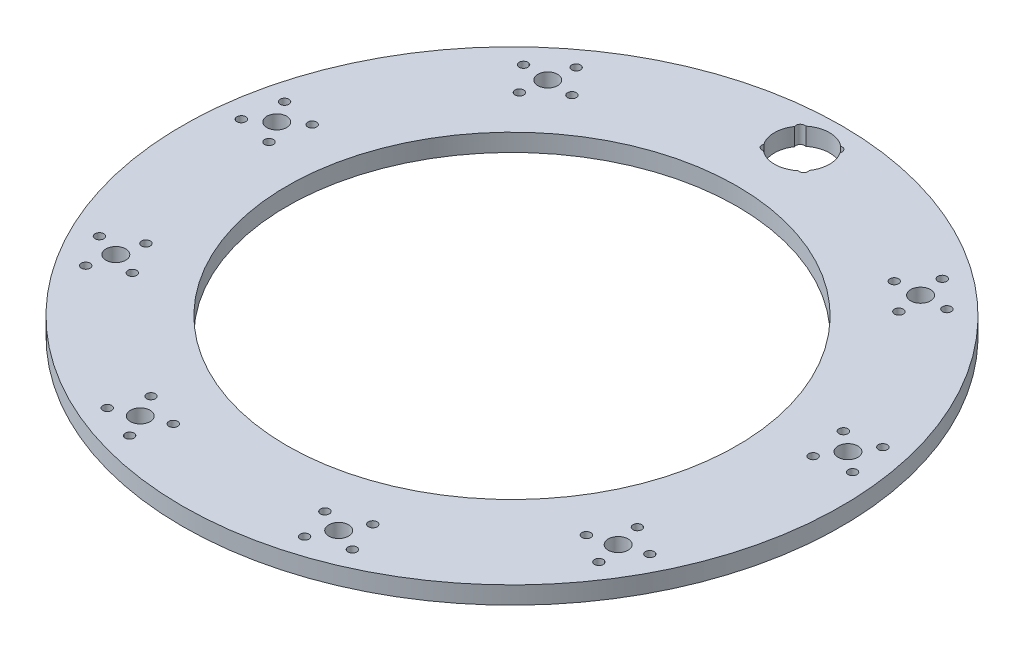
SolidWorks part; units mm, degrees
material "Balsa"
ref_plane "Ebene vorne" through (0, 0, 0) normal (0, 0, 1) x (1, 0, 0)
ref_plane "Ebene oben" through (0, 0, 0) normal (0, 1, 0) x (1, 0, 0)
ref_plane "Ebene rechts" through (0, 0, 0) normal (1, 0, 0) x (0, 0, -1)
sketch "Sketch1" plane through (0, 0, 0) normal (0, 1, 0) x (1, 0, 0)
  circle A0 centre (0, 0) radius 51.2
  circle A1 centre (0, 0) radius 75
  dimension "D1" = 150
  dimension "D2" = 102.4
extrude "Boss-Extrude1" add sketch "Sketch1" along normal blind 4
sketch "Sketch2" plane through (0, 4, 0) normal (0, 1, 0) x (1, 0, 0)
  line L0 (0, 78.5044) -> (0, 60.1888) construction
  line L1 (7.9546, 66) -> (-11.9341, 66) construction
  circle A0 centre (0, 66) radius 2.25
  circle A1 centre (4.2466, 69.8767) radius 1
  circle A2 centre (4.2466, 62.1233) radius 1
  circle A3 centre (-4.2466, 62.1233) radius 1
  circle A4 centre (-4.2466, 69.8767) radius 1
  dimension "D1" = 4.5
  dimension "D3" = 2
  dimension "D2" = 11.5
  dimension "D4" = 66
extrude "Cut-Extrude1" cut sketch "Sketch2" against normal through all
ref_axis "Axis1" through (0, -0.2, 0) along (0, 1, 0)
pattern_circular "CirPattern1" count 9 over 360 about axis through (0, -0.2, 0) along (0, 1, 0) of "Cut-Extrude1"
sketch "Sketch3" plane through (0, 4, 0) normal (0, 1, 0) x (1, 0, 0)
  line L0 (0, 66) -> (0, 0) construction
  circle A0 centre (0, 66) radius 6.25
  dimension "D1" = 12.5
  dimension "D2" = 66
extrude "Cut-Extrude2" cut sketch "Sketch3" against normal blind 10
equation "\"d_i_tube\"= 150mm'Inner Rocket Body Composite Tube Diameter"
equation "\"t_tube\"= 1.182mm'Thickness of Rocket Body Composite Tube"
equation "\"l_upper_body_tube\"= 1190mm'Upper Rocket Body Composite Tube length"
equation "\"l_lower_body_tube\"= 896mm'Lower Rocket Body Composite Tube Length"
equation "\"d_a_NC\"= 154mm'Outer Diameter of Nosecone base"
equation "\"d_i_phenolic_tube\"= 152.3mm'Inner Phenolic Tube Diameter"
equation "\"t_phenolic_tube\"= 2mm'Thickness of Phenolic Body Tube"
equation "\"l_fin_cut\"= 220mm'Length of fin on Motor Retainer"
equation "\"t_SW-Panel\"= 11.482mm'Thickness of Sandwich-Panel"
equation "\"l_motor_tube\"=650mm'Length of phenolic motor tube"
equation "\"d_i_motor_tube\"=99.06mm'Inner diameter of phenolic motor tube"
equation "\"t_motor_tube\"=1.58mm'Thicknes of phenolic motor tube"
equation "\"D1@Sketch1\"=\"d_i_tube\""
